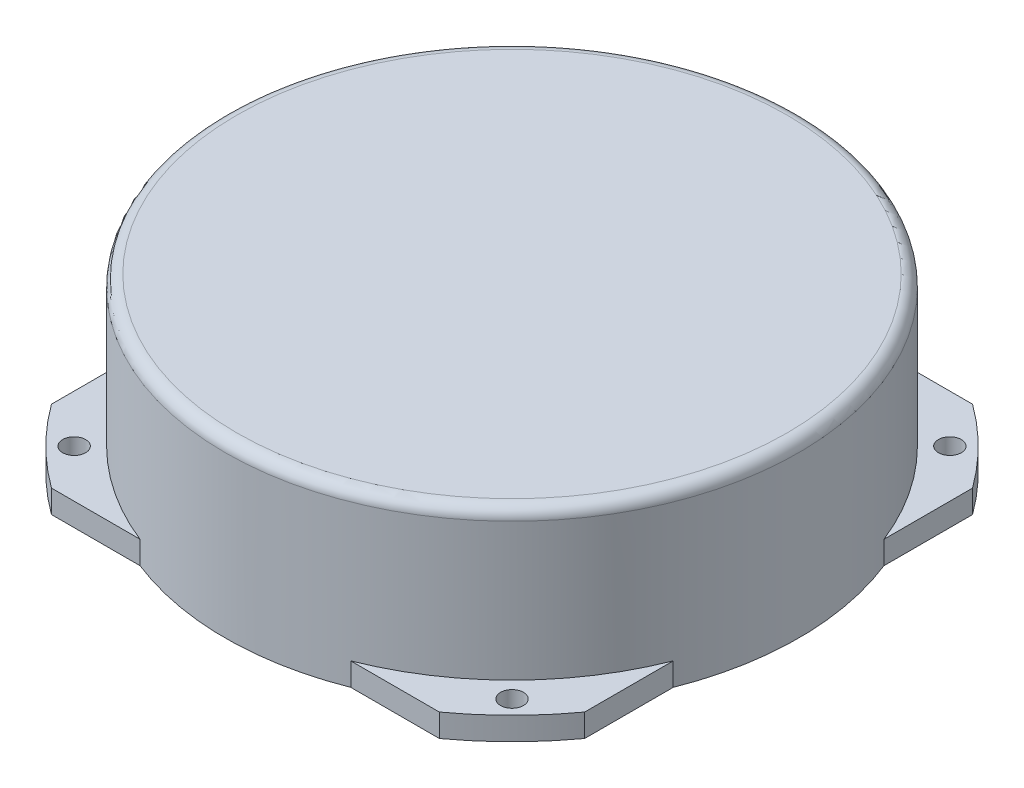
SolidWorks part; units mm, degrees
ref_plane "Front Plane" through (0, 0, 0) normal (0, 0, 1) x (1, 0, 0)
ref_plane "Top Plane" through (0, 0, 0) normal (0, 1, 0) x (1, 0, 0)
ref_plane "Right Plane" through (0, 0, 0) normal (1, 0, 0) x (0, 0, -1)
sketch "Sketch1" plane through (0, 0, 0) normal (0, 1, 0) x (1, 0, 0)
  line L22 (-18.378, -46.5) -> (-33.8231, -46.5)
  line L23 (-46.5, 18.378) -> (-46.5, 33.8231)
  line L24 (-33.8231, 46.5) -> (-18.378, 46.5)
  line L25 (46.5, 33.8231) -> (46.5, 18.378)
  line L26 (33.8231, -46.5) -> (18.378, -46.5)
  line L27 (-46.5, -33.8231) -> (-46.5, -18.378)
  line L28 (46.5, -18.378) -> (46.5, -33.8231)
  line L29 (18.378, 46.5) -> (33.8231, 46.5)
  circle A0 centre (0, 0) radius 50
  arc A1 (-33.8231, 46.5) -> (-46.5, 33.8231) centre (0, 0) ccw
  arc A3 (-46.5, -33.8231) -> (-33.8231, -46.5) centre (0, 0) ccw
  arc A4 (33.8231, -46.5) -> (46.5, -33.8231) centre (0, 0) ccw
  arc A5 (46.5, 33.8231) -> (33.8231, 46.5) centre (0, 0) ccw
  circle A7 centre (-38.1838, 38.1838) radius 2
  circle A8 centre (38.1838, 38.1838) radius 2
  circle A9 centre (38.1838, -38.1838) radius 2
  circle A10 centre (-38.1838, -38.1838) radius 2
  point P7 (-38.1838, 38.1838)
  point P17 (-40.6586, 40.6586)
  point P20 (40.6586, 40.6586)
  point P38 (0, 0)
  dimension "D1" = 4
extrude "Boss-Extrude1" add sketch "Sketch1" along normal blind 30 contours A0
extrude "Boss-Extrude2" add sketch "Sketch1<3>" along normal blind 4 contours L24 A1 L23 A0 A7 | L27 A3 L22 A0 A10 | L26 A4 L28 A0 A9 | L25 A5 L29 A0 A8 region at (-26.1005, 0, 46.1023) region at (35.6366, 0, 35.6366) region at (-46.1023, 0, -26.1005) region at (26.1005, 0, -46.1023)
sketch "Sketch1<3>" plane through (0, 0, 0) normal (0, 1, 0) x (1, 0, 0) same geometry as "Sketch1"
fillet "Fillet2" radius 2 1 edges at (0, 30, 50)
